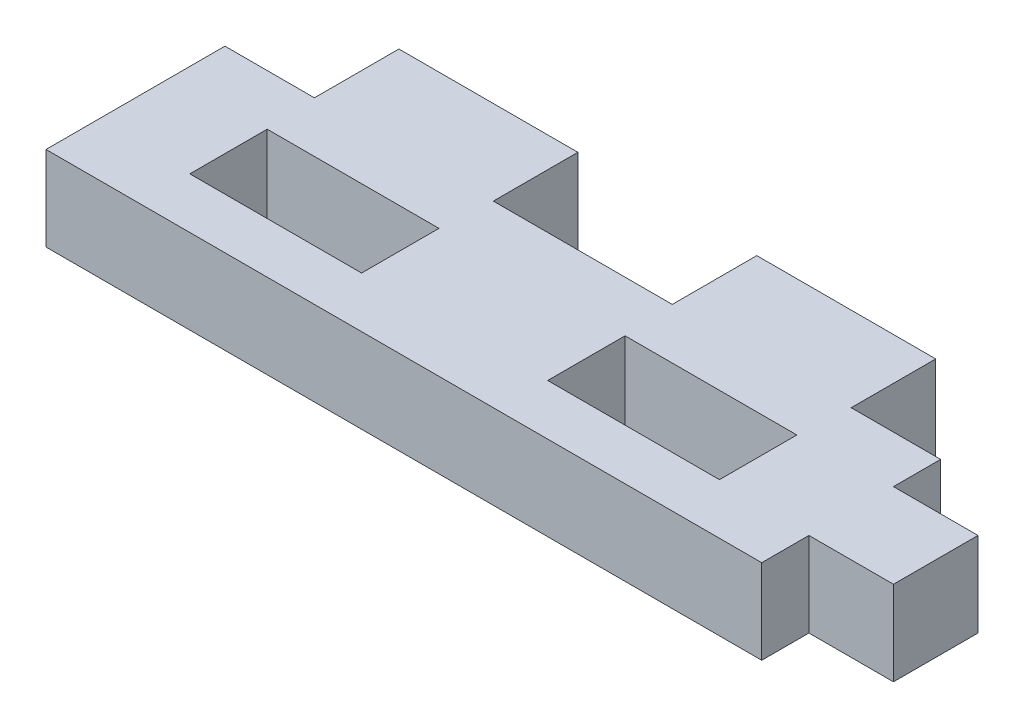
SolidWorks part; units mm, degrees
ref_plane "Front Plane" through (0, 0, 0) normal (0, 0, 1) x (1, 0, 0)
ref_plane "Top Plane" through (0, 0, 0) normal (0, 1, 0) x (1, 0, 0)
ref_plane "Right Plane" through (0, 0, 0) normal (1, 0, 0) x (0, 0, -1)
sketch "Sketch1" plane through (0, 0, 0) normal (0, 1, 0) x (1, 0, 0)
  line L0 (3.175, 3.175) -> (6.35, 3.175)
  line L1 (-3.048, -1.373) -> (3.048, -1.373)
  line L2 (-3.048, -1.373) -> (-3.048, 1.373)
  line L3 (-3.048, 1.373) -> (3.048, 1.373)
  line L4 (3.048, -1.373) -> (3.048, 1.373)
  line L5 (-3.048, -1.373) -> (3.048, 1.373) construction
  line L6 (-3.048, 1.373) -> (3.048, -1.373) construction
  line L7 (-6.35, -3.175) -> (6.35, -3.175)
  line L8 (-6.35, -3.175) -> (-6.35, 3.175) construction
  line L9 (-6.35, 3.175) -> (-3.175, 3.175)
  line L10 (6.35, -3.175) -> (6.35, -1.5)
  line L11 (-6.35, -3.175) -> (6.35, 3.175) construction
  line L12 (-6.35, 3.175) -> (6.35, -3.175) construction
  line L13 (-3.175, 6.175) -> (3.175, 6.175)
  line L14 (-3.175, 6.175) -> (-3.175, 3.175)
  line L16 (3.175, 6.175) -> (3.175, 3.175)
  line L17 (-3.175, 6.175) -> (3.175, 3.175) construction
  line L18 (-3.175, 3.175) -> (3.175, 6.175) construction
  line L19 (9.35, -1.5) -> (6.35, -1.5)
  line L20 (9.35, -1.5) -> (9.35, 1.5)
  line L21 (9.35, 1.5) -> (6.35, 1.5)
  line L23 (9.35, -1.5) -> (6.35, 1.5) construction
  line L24 (9.35, 1.5) -> (6.35, -1.5) construction
  line L25 (6.35, 1.5) -> (6.35, 3.175)
  line L26 (-9.525, 3.175) -> (-6.35, 3.175)
  line L27 (-19.05, -3.175) -> (-6.35, -3.175)
  line L28 (-19.05, -3.175) -> (-19.05, 3.175)
  line L29 (-19.05, 3.175) -> (-15.875, 3.175)
  line L31 (-19.05, -3.175) -> (-6.35, 3.175) construction
  line L32 (-19.05, 3.175) -> (-6.35, -3.175) construction
  line L33 (-15.875, 6.175) -> (-9.525, 6.175)
  line L34 (-15.875, 6.175) -> (-15.875, 3.175)
  line L36 (-9.525, 6.175) -> (-9.525, 3.175)
  line L37 (-15.875, 6.175) -> (-9.525, 3.175) construction
  line L38 (-15.875, 3.175) -> (-9.525, 6.175) construction
  line L40 (-15.748, 1.373) -> (-9.652, 1.373)
  line L41 (-15.748, 1.373) -> (-15.748, -1.373)
  line L42 (-15.748, -1.373) -> (-9.652, -1.373)
  line L43 (-9.652, 1.373) -> (-9.652, -1.373)
  line L44 (-15.748, 1.373) -> (-9.652, -1.373) construction
  line L45 (-15.748, -1.373) -> (-9.652, 1.373) construction
  point P0 (0, 0)
  point P6 (0, 0)
  point P11 (0, 4.675)
  point P16 (7.85, 0)
  point P21 (-12.7, 0)
  point P25 (-12.7, 4.675)
  point P26 (-12.7, 0)
  dimension "D1" = 2.746
  dimension "D2" = 6.096
  dimension "D3" = 12.7
  dimension "D4" = 6.35
  dimension "D5" = 6.35
  dimension "D6" = 3
  dimension "D7" = 3
  dimension "D8" = 3
extrude "Boss-Extrude1" add sketch "Sketch1" along normal mid plane 3
